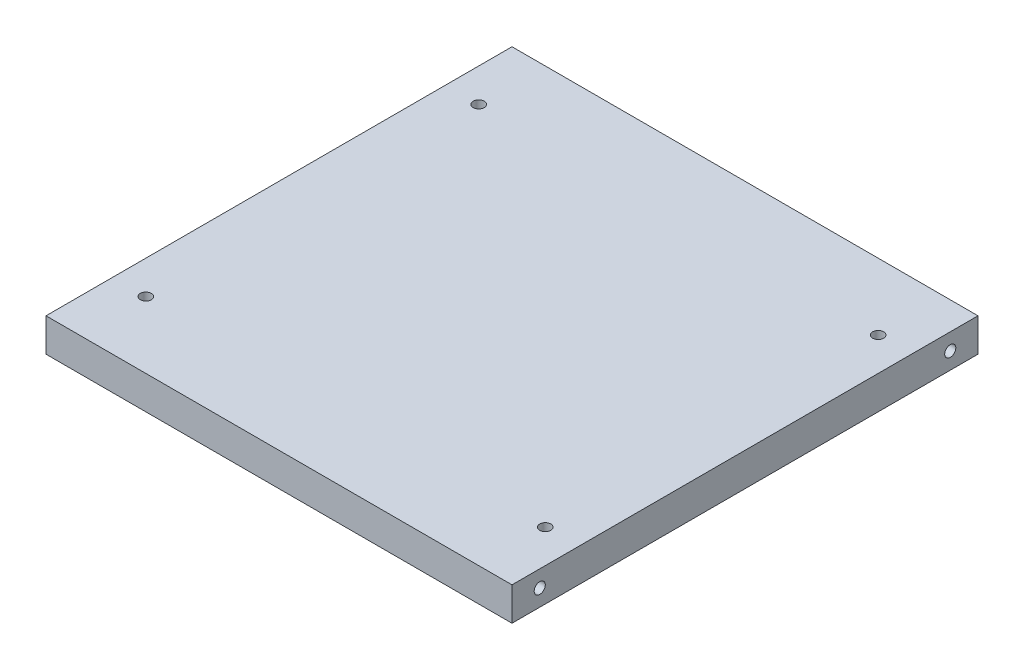
SolidWorks part; units mm, degrees
material "AISI 1020"
ref_plane "Front Plane" through (0, 0, 0) normal (0, 0, 1) x (1, 0, 0)
ref_plane "Top Plane" through (0, 0, 0) normal (0, 1, 0) x (1, 0, 0)
ref_plane "Right Plane" through (0, 0, 0) normal (1, 0, 0) x (0, 0, -1)
sketch "Sketch1" plane through (0, 0, 0) normal (0, 1, 0) x (1, 0, 0)
  line L1 (0, 0) -> (84, 0)
  line L2 (0, 0) -> (0, 84)
  line L3 (0, 84) -> (84, 84)
  line L4 (84, 0) -> (84, 84)
  dimension "D1" = 84
  dimension "D2" = 84
extrude "Boss-Extrude1" add sketch "Sketch1" along normal blind 6
sketch "Sketch2" plane through (0, 6, 0) normal (0, 1, 0) x (1, 0, 0)
  line L0 (84, 84) -> (0, 84) construction
  line L1 (0, 84) -> (0, 0) construction
  circle A0 centre (6, 72) radius 1
  dimension "D1" = 2
  dimension "D3" = 6
  dimension "D2" = 12
extrude "Cut-Extrude1" cut sketch "Sketch2" against normal blind 6
pattern_linear "LPattern1" count 2 spacing 72 along (1, 0, 0) count 2 spacing 60 along (0, 0, 1) of "Cut-Extrude1"
sketch "Sketch3" plane through (0, 0, 0) normal (-1, 0, 0) x (0, 0, 1)
  line L0 (-84, 3) -> (-5, 3) construction
  line L1 (-84, 6) -> (-84, 0) construction
  line L2 (0, 6) -> (0, 0) construction
  circle A0 centre (-79, 3) radius 1
  circle A1 centre (-5, 3) radius 1
  dimension "D1" = 5
  dimension "D3" = 2
  dimension "D4" = 2
  dimension "D2" = 5
extrude "Cut-Extrude2" cut sketch "Sketch3" against normal blind 10
ref_plane "Plane1" through (42, 0, 0) normal (-1, 0, 0) x (0, 0, 1)
mirror "Mirror1" about plane through (42, 0, 0) normal (-1, 0, 0) of "Cut-Extrude2"
